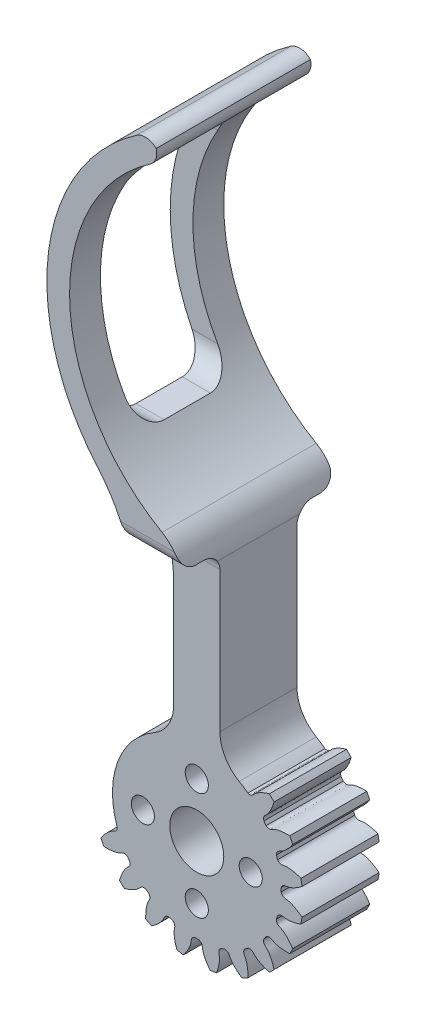
SolidWorks part; units mm, degrees
material "聚脂树脂"
ref_plane "前视基准面" through (0, 0, 0) normal (0, 0, 1) x (1, 0, 0)
ref_plane "上视基准面" through (0, 0, 0) normal (0, 1, 0) x (1, 0, 0)
ref_plane "右视基准面" through (0, 0, 0) normal (1, 0, 0) x (0, 0, -1)
other "Configuration Table"
sketch "草图1" plane through (0, 0, 0) normal (0, 0, 1) x (1, 0, 0)
  circle A0 centre (0, 0) radius 13.75
extrude "凸台-拉伸1" add sketch "草图1" along normal blind 10
ref_axis "基准轴1" through (0, 0, -1.5) along (0, 0, 1)
sketch "草图2" plane through (0, 0, 0) normal (0, 0, 1) x (1, 0, 0)
  line L0 (0, 0) -> (0, 13.75) construction
  circle A0 centre (0, 0) radius 13.75 construction
  arc A1 (0.2416, 10.9348) -> (-0.2416, 10.9348) centre (0, 0) ccw
  arc A2 (3.9764, 15.6228) -> (-3.9764, 15.6228) centre (0, 0) ccw
  spline S0 degree 3 poles (0.2416, 10.9348) (0.764, 11.1168) (0.6964, 11.4839) (0.7661, 11.8375) (0.7736, 11.8719) (0.7829, 11.9108) (0.7941, 11.954) (0.8075, 12.0015) (0.8231, 12.0532) (0.8413, 12.1091) (0.8621, 12.169) (0.8857, 12.2329) (0.9123, 12.3007) (0.9421, 12.3723) (0.9752, 12.4476) (1.0117, 12.5264) (1.0519, 12.6088) (1.0959, 12.6945) (1.1438, 12.7834) (1.1957, 12.8755) (1.2519, 12.9705) (1.3125, 13.0684) (1.3775, 13.1691) (1.4472, 13.2723) (1.5216, 13.3779) (1.601, 13.4858) (1.6853, 13.5958) (1.7747, 13.7078) (1.8694, 13.8216) (1.9693, 13.937) (2.0748, 14.0539) (2.1857, 14.1721) (2.3023, 14.2914) (2.4246, 14.4116) (2.5527, 14.5326) (2.6866, 14.6542) (2.8265, 14.7761) (2.9725, 14.8983) (3.1245, 15.0204) (3.2826, 15.1424) (3.4469, 15.2639) (3.6768, 15.427) (3.8549, 15.5454) (3.9764, 15.6228) knots 0 0 0 0 0.165916 0.170906 0.176664 0.183189 0.190482 0.198542 0.207371 0.216967 0.22733 0.238462 0.250361 0.263027 0.276462 0.290664 0.305634 0.321371 0.337876 0.355149 0.37319 0.391998 0.411574 0.431917 0.453028 0.474907 0.497554 0.520968 0.54515 0.570099 0.595817 0.622302 0.649554 0.677575 0.706363 0.735918 0.766242 0.797333 0.829191 0.861818 0.895212 0.929373 1 1 1 1
  spline S1 degree 3 poles (-0.2416, 10.9348) (-0.764, 11.1168) (-0.6964, 11.4839) (-0.7661, 11.8375) (-0.7736, 11.8719) (-0.7829, 11.9108) (-0.7941, 11.954) (-0.8075, 12.0015) (-0.8231, 12.0532) (-0.8413, 12.1091) (-0.8621, 12.169) (-0.8857, 12.2329) (-0.9123, 12.3007) (-0.9421, 12.3723) (-0.9752, 12.4476) (-1.0117, 12.5264) (-1.0519, 12.6088) (-1.0959, 12.6945) (-1.1438, 12.7834) (-1.1957, 12.8755) (-1.2519, 12.9705) (-1.3125, 13.0684) (-1.3775, 13.1691) (-1.4472, 13.2723) (-1.5216, 13.3779) (-1.601, 13.4858) (-1.6853, 13.5958) (-1.7747, 13.7078) (-1.8694, 13.8216) (-1.9693, 13.937) (-2.0748, 14.0539) (-2.1857, 14.1721) (-2.3023, 14.2914) (-2.4246, 14.4116) (-2.5527, 14.5326) (-2.6866, 14.6542) (-2.8265, 14.7761) (-2.9725, 14.8983) (-3.1245, 15.0204) (-3.2826, 15.1424) (-3.4469, 15.2639) (-3.6768, 15.427) (-3.8549, 15.5454) (-3.9764, 15.6228) knots 0 0 0 0 0.165916 0.170906 0.176664 0.183189 0.190482 0.198542 0.207371 0.216967 0.22733 0.238462 0.250361 0.263027 0.276462 0.290664 0.305634 0.321371 0.337876 0.355149 0.37319 0.391998 0.411574 0.431917 0.453028 0.474907 0.497554 0.520968 0.54515 0.570099 0.595817 0.622302 0.649554 0.677575 0.706363 0.735918 0.766242 0.797333 0.829191 0.861818 0.895212 0.929373 1 1 1 1
extrude "切除-拉伸1" cut sketch "草图2" along normal through all
pattern_circular "阵列(圆周)1" count 20 every 18 about axis through (0, 0, -1.5) along (0, 0, 1) of "切除-拉伸1"
sketch "草图3" plane through (0, 0, 0) normal (0, 0, 1) x (1, 0, 0)
  circle A0 centre (0, 0) radius 12.5 construction
  dimension "Dn" = 25
sketch "草图6" plane through (0, 0, 0) normal (0, 0, -1) x (-1, 0, 0)
  line L0 (0, 0) -> (0, 65.9124) construction
  line L1 (0, 0) -> (39.45, 0) construction
  line L2 (0, 0) -> (-30.8379, 0) construction
  line L3 (-12.5, 0) -> (-12.5, 56.4778) construction
  line L4 (3, 0) -> (3, 36.1803)
  line L5 (-3, 0) -> (-3, 36.1803)
  line L6 (-3, 36.1803) -> (-3, 74.6745)
  line L7 (-3, 74.6745) -> (-12.5, 58.22) construction
  line L8 (-3, 74.6745) -> (6.3052, 90.7916) construction
  line L9 (-3, 74.6745) -> (0.9722, 81.5545)
  line L10 (-3, 0) -> (3, 0)
  line L11 (-5.8534, 12.4419) -> (-3, 14.0893)
  line L12 (5.8534, 12.4419) -> (3, 14.0893)
  circle A0 centre (0, 0) radius 12.5 construction
  circle A1 centre (-12.5, 58.22) radius 24 construction
  circle A2 centre (-12.5, 58.22) radius 26.9444 construction
  arc A3 (0.9722, 81.5545) -> (3, 36.1803) centre (-12.5, 58.22) cw
  arc A4 (-0.5, 79.0046) -> (-3, 36.1803) centre (-12.5, 58.22) cw
  spline S0 degree 3 poles (1668.4324, 1107.449) (-22.4355, -9.6532) (-2.0511, 6.8358) (-4.3931, 11.033) (-4.4189, 11.076) (-4.4589, 11.1387) (-4.5098, 11.2131) (-4.5827, 11.3111) (-4.6712, 11.4208) (-4.7765, 11.541) (-4.8994, 11.6706) (-5.0408, 11.8083) (-5.2016, 11.9528) (-5.3825, 12.1027) (-5.5474, 12.2287) (-5.6899, 12.331) (-25.6073, 26.0378) (-114.7142, -63.0586) (1854.1098, 747.2788) knots -2.172632 -2.172632 -2.172632 -2.172632 0.165916 0.170906 0.183189 0.190482 0.207371 0.22733 0.250361 0.276462 0.305634 0.337876 0.37319 0.411574 0.453028 0.474907 0.497554 12.30377 12.30377 12.30377 12.30377 only from (-3.6089, 10.325) to (-5.8534, 12.4419) construction
  spline S1 degree 3 poles (-3, 10.4088) (-4.144, 10.1273) (-4.1641, 10.6226) (-4.3931, 11.033) (-4.4189, 11.076) (-4.4589, 11.1387) (-4.5098, 11.2131) (-4.5827, 11.3111) (-4.6712, 11.4208) (-4.7765, 11.541) (-4.8994, 11.6706) (-5.0408, 11.8083) (-5.2016, 11.9528) (-5.3825, 12.1027) (-5.5842, 12.2567) (-5.7442, 12.3691) (-5.8366, 12.4308) (-5.8534, 12.4419) knots -0.047197 -0.047197 -0.047197 -0.047197 0.165916 0.170906 0.183189 0.190482 0.207371 0.22733 0.250361 0.276462 0.305634 0.337876 0.37319 0.411574 0.453028 0.497554 0.507432 0.507432 0.507432 0.507432
  spline S2 degree 3 poles (-1668.4324, 1107.449) (22.4355, -9.6532) (2.0511, 6.8358) (4.3931, 11.033) (4.4189, 11.076) (4.4589, 11.1387) (4.5098, 11.2131) (4.5827, 11.3111) (4.6712, 11.4208) (4.7765, 11.541) (4.8994, 11.6706) (5.0408, 11.8083) (5.2016, 11.9528) (5.3825, 12.1027) (5.5474, 12.2287) (5.6899, 12.331) (25.6073, 26.0378) (114.7142, -63.0586) (-1854.1098, 747.2788) knots -1.680063 -1.680063 -1.680063 -1.680063 0.658484 0.663474 0.675757 0.68305 0.699939 0.719899 0.742929 0.76903 0.798202 0.830445 0.865758 0.904142 0.945597 0.967475 0.990122 12.796339 12.796339 12.796339 12.796339 only from (3.6089, 10.325) to (5.8534, 12.4419) construction
  spline S3 degree 3 poles (3, 10.4088) (4.144, 10.1273) (4.1641, 10.6226) (4.3931, 11.033) (4.4189, 11.076) (4.4589, 11.1387) (4.5098, 11.2131) (4.5827, 11.3111) (4.6712, 11.4208) (4.7765, 11.541) (4.8994, 11.6706) (5.0408, 11.8083) (5.2016, 11.9528) (5.3825, 12.1027) (5.5842, 12.2567) (5.7442, 12.3691) (5.8366, 12.4308) (5.8534, 12.4419) knots 0.445372 0.445372 0.445372 0.445372 0.658484 0.663474 0.675757 0.68305 0.699939 0.719899 0.742929 0.76903 0.798202 0.830445 0.865758 0.904142 0.945597 0.990122 1 1 1 1
  dimension "D1" = 25
  dimension "D4" = 48
  dimension "D5" = 30
  dimension "D2" = 6
  dimension "D3" = 58.22
  dimension "D6" = 60
  dimension "D7" = 60
extrude "凸台-拉伸2" add sketch "草图6" against normal blind 15 and the other way blind 5 contours A3 L9 L6 L5 L10 L4 | S1 L5 L11 | L4 S3 L12 region at (0, 0.834, 0) region at (-3.9534, 12.128, 0) region at (3.9534, 12.128, 0)
sketch "草图7" plane through (3, 0, 0) normal (1, 0, 0) x (0, 0, -1)
  line L0 (0, 0) -> (0, 34)
  line L1 (0, 34) -> (5, 34)
  line L3 (5, 34) -> (5, 0)
  line L4 (5, 0) -> (0, 0) construction
  line L5 (5, 0) -> (5, 10.4088) construction
  line L6 (5, 0) -> (0, 0)
  line L7 (-5, 2.5777) -> (-5, 27.3083) construction
  line L8 (-10, 2.5777) -> (0, 2.5777) construction
  line L9 (-15, 34) -> (-15, 0)
  line L10 (-10, 34) -> (-15, 34)
  line L11 (-10, 0) -> (-10, 34)
  line L12 (-15, 0) -> (-10, 0)
  dimension "D1" = 34
extrude "切除-拉伸3" cut sketch "草图7" against normal blind 32 and the other way blind 10
ref_plane "基准面1" through (12.5, 0, 0) normal (1, 0, 0) x (0, 0, -1)
fillet "圆角2" radius 2 4 edges at (0, 34, 10) (0, 34, 15) (0, 34, 0) (0, 34, -5)
sketch "草图4" plane through (0, 0, 10) normal (0, 0, 1) x (1, 0, 0)
  line L0 (0, 0) -> (0, 14.4175) construction
  line L1 (0, 0) -> (19.7904, 0) construction
  circle A0 centre (0, 0) radius 9
  circle A1 centre (0, 0) radius 3.5
  circle A2 centre (0, 7) radius 1.5
  circle A3 centre (7, 0) radius 1.5
  circle A4 centre (0, -7) radius 1.5
  circle A5 centre (-7, 0) radius 1.5
  dimension "D1" = 18
  dimension "D2" = 7
  dimension "D3" = 3
  dimension "D4" = 3
  dimension "D5" = 7
  dimension "D6" = 7
extrude "切除-拉伸2" cut sketch "草图4" against normal blind 20 contours A1 | A5 | A2 | A3 | A4
ref_plane "基准面2" through (0, 0, 9) normal (0, 0, 1) x (1, 0, 0)
sketch "草图17" plane through (0, 0, 10) normal (0, 0, 1) x (1, 0, 0)
  line L0 (0, 0) -> (-6.6228, 8.7044)
  line L1 (-6.6228, 8.7044) -> (-11.857, 15.5837)
  line L2 (0, 0) -> (-10.325, -3.6089)
  line L3 (-10.325, -3.6089) -> (-17.9409, -6.2709)
  circle A0 centre (0, 0) radius 10.9375
  arc A1 (-6.2318, 8.9885) -> (-6.6228, 8.7044) centre (0, 0) ccw construction
  circle A2 centre (0, 0) radius 17.5
  dimension "D1" = 35
extrude "切除-拉伸5" cut sketch "草图17" against normal blind 10 contours L1 A2 L3 A0 region at (-12.9643, 3.8979, 10)
fillet "圆角3" radius 20 1 edges at (-3, 36.1803, 5)
fillet "圆角4" radius 5 1 edges at (3, 36.1803, 5)
fillet "圆角5" radius 2 2 edges at (-0.9722, 81.5545, 5) (0.5, 79.0046, 5)
sketch "草图19" plane through (12.5, 0, 0) normal (1, 0, 0) x (0, 0, -1)
  line L0 (-5, 0.2416) -> (-5, 85.5937) construction
  line L1 (-10, 0.2416) -> (0, 0.2416) construction
  line L2 (5, 37.4354) -> (5, 78.0199) construction
  line L5 (-11, 43.22) -> (1, 43.22)
  line L6 (-11, 43.22) -> (-11, 73.22)
  line L7 (-11, 73.22) -> (1, 73.22)
  line L8 (1, 43.22) -> (1, 73.22)
  line L9 (-11, 43.22) -> (1, 73.22) construction
  line L10 (-11, 73.22) -> (1, 43.22) construction
  point P4 (-5, 58.22)
  dimension "D3" = 4
  dimension "D1" = 30
  dimension "D2" = 58.22
extrude "切除-拉伸6" cut sketch "草图19" against normal blind 55
fillet "圆角6" radius 3 4 edges at (-8.059, 43.22, -1) (-8.059, 43.22, 11) (-8.059, 73.22, 11) (-8.059, 73.22, -1)
sketch "草图20" plane through (0, 0, 0) normal (0, 0, -1) x (-1, 0, 0)
  line L0 (-3, 14.0893) -> (-3, 10.518)
  line L1 (3, 14.0893) -> (3, 10.518)
  line L2 (5.8534, 12.4419) -> (3, 14.0893) construction
  line L3 (-5.8534, 12.4419) -> (-3, 14.0893) construction
  line L4 (5.8534, 12.4419) -> (3, 14.0893)
  line L5 (-5.8534, 12.4419) -> (-3, 14.0893)
  circle A0 centre (0, 0) radius 10.9375
  arc A1 (10.325, -3.6089) -> (6.2318, 8.9885) centre (0, 0) ccw construction
  arc A2 (6.6252, 12.0486) -> (5.8534, 12.4419) centre (0, 0) ccw construction
  arc A3 (-5.8534, 12.4419) -> (-6.6252, 12.0486) centre (0, 0) ccw construction
  arc A4 (6.6252, 12.0486) -> (5.8534, 12.4419) centre (0, 0) ccw
  arc A5 (-5.8534, 12.4419) -> (-6.6252, 12.0486) centre (0, 0) ccw
  spline S0 degree 3 poles (940.4852, -347.6041) (-11.6727, 10.1742) (4.7326, 6.5586) (6.3437, 10.0391) (6.3633, 10.0853) (6.3905, 10.1545) (6.4208, 10.2394) (6.4573, 10.356) (6.4939, 10.4921) (6.5293, 10.6479) (6.5619, 10.8235) (6.5902, 11.0188) (6.6126, 11.2338) (6.6276, 11.4683) (6.6325, 11.6758) (6.6315, 11.8512) (6.1325, 31.3668) (-75.0291, 47.9678) (845.3646, -532.4841) knots -1.696649 -1.696649 -1.696649 -1.696649 0.165916 0.170906 0.183189 0.190482 0.207371 0.22733 0.250361 0.276462 0.305634 0.337876 0.37319 0.411574 0.453028 0.474907 0.497554 10.021595 10.021595 10.021595 10.021595 only from (6.2318, 8.9885) to (6.6252, 12.0486) construction
  spline S1 degree 3 poles (-940.4852, -347.6041) (11.6727, 10.1742) (-4.7326, 6.5586) (-6.3437, 10.0391) (-6.3633, 10.0853) (-6.3905, 10.1545) (-6.4208, 10.2394) (-6.4573, 10.356) (-6.4939, 10.4921) (-6.5293, 10.6479) (-6.5619, 10.8235) (-6.5902, 11.0188) (-6.6126, 11.2338) (-6.6276, 11.4683) (-6.6325, 11.6758) (-6.6315, 11.8512) (-6.1325, 31.3668) (75.0291, 47.9678) (-845.3646, -532.4841) knots -1.204081 -1.204081 -1.204081 -1.204081 0.658484 0.663474 0.675757 0.68305 0.699939 0.719899 0.742929 0.76903 0.798202 0.830445 0.865758 0.904142 0.945597 0.967475 0.990122 10.514164 10.514164 10.514164 10.514164 only from (-6.2318, 8.9885) to (-6.6252, 12.0486) construction
  spline S2 degree 3 poles (6.2318, 8.9885) (5.9162, 9.4428) (6.1867, 9.7) (6.3437, 10.0391) (6.3633, 10.0853) (6.3905, 10.1545) (6.4208, 10.2394) (6.4573, 10.356) (6.4939, 10.4921) (6.5293, 10.6479) (6.5619, 10.8235) (6.5902, 11.0188) (6.6126, 11.2338) (6.6276, 11.4683) (6.6336, 11.722) (6.6305, 11.9176) (6.6261, 12.0285) (6.6252, 12.0486) knots 0 0 0 0 0.165916 0.170906 0.183189 0.190482 0.207371 0.22733 0.250361 0.276462 0.305634 0.337876 0.37319 0.411574 0.453028 0.497554 0.507432 0.507432 0.507432 0.507432
  spline S3 degree 3 poles (-6.2318, 8.9885) (-5.9162, 9.4428) (-6.1867, 9.7) (-6.3437, 10.0391) (-6.3633, 10.0853) (-6.3905, 10.1545) (-6.4208, 10.2394) (-6.4573, 10.356) (-6.4939, 10.4921) (-6.5293, 10.6479) (-6.5619, 10.8235) (-6.5902, 11.0188) (-6.6126, 11.2338) (-6.6276, 11.4683) (-6.6336, 11.722) (-6.6305, 11.9176) (-6.6261, 12.0285) (-6.6252, 12.0486) knots 0.492568 0.492568 0.492568 0.492568 0.658484 0.663474 0.675757 0.68305 0.699939 0.719899 0.742929 0.76903 0.798202 0.830445 0.865758 0.904142 0.945597 0.990122 1 1 1 1
extrude "切除-拉伸7" cut sketch "草图20" against normal blind 10 contours S3 A0 L0 L5 A5 | A0 S2 A4 L4 L1 region at (4.6909, 11.5198, 0) region at (-4.6909, 11.5198, 0)
fillet "圆角7" radius 5 2 edges at (-3, 10.518, 5) (3, 10.518, 5)
